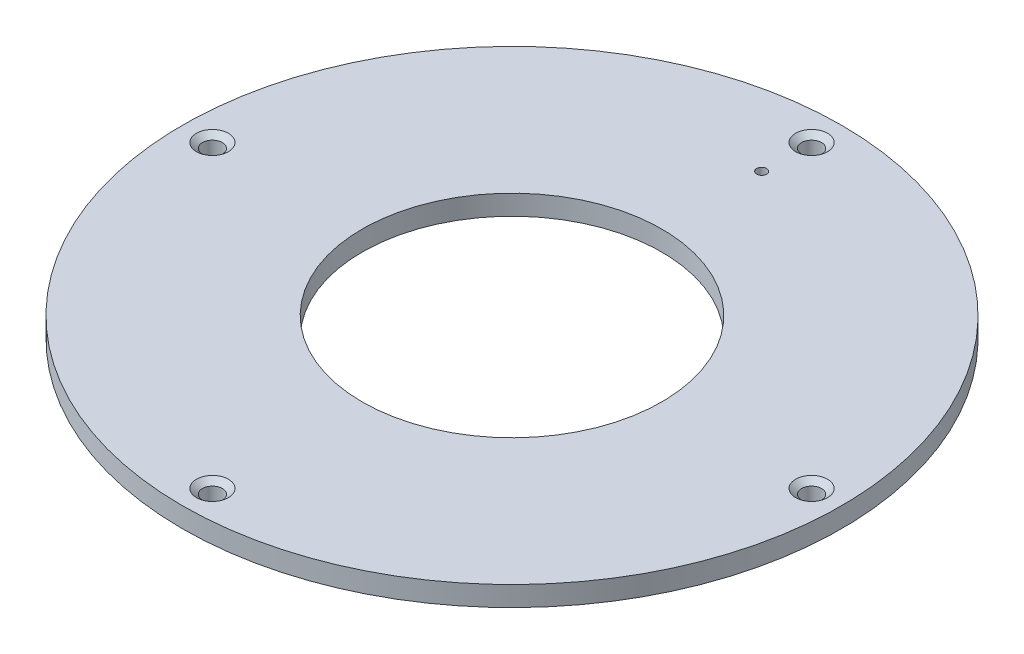
SolidWorks part; units mm, degrees
material "1060 Alloy"
ref_plane "Front Plane" through (0, 0, 0) normal (0, 0, 1) x (1, 0, 0)
ref_plane "Top Plane" through (0, 0, 0) normal (0, 1, 0) x (1, 0, 0)
ref_plane "Right Plane" through (0, 0, 0) normal (1, 0, 0) x (0, 0, -1)
sketch "Sketch1" plane through (0, 0, 0) normal (0, 1, 0) x (1, 0, 0)
  circle A0 centre (0, 0) radius 16.5
  dimension "D1" = 33
extrude "Boss-Extrude1" add sketch "Sketch1" along normal blind 1
sketch "Sketch2" plane through (0, 1, 0) normal (0, 1, 0) x (1, 0, 0)
  circle A0 centre (0, 0) radius 7.5
  dimension "D1" = 15
extrude "Cut-Extrude1" cut sketch "Sketch2" against normal through all both and the other way through all
ref_plane "Plane2" through (0, 0.5, 0) normal (0, 1, 0) x (1, 0, 0)
sketch "Sketch4" plane through (0, 1, 0) normal (0, 1, 0) x (1, 0, 0)
  circle A0 centre (0, 12.5) radius 0.25
  dimension "D1" = 0.5
  dimension "D2" = 12.5
extrude "Cut-Extrude2" cut sketch "Sketch4" against normal through all both and the other way through all
hole_wizard "CSK for M2 Flat Head Machine Screw1" positions "Sketch5" profile "Sketch6" countersink size "M2" standard "ANSI Metric" end condition through all
sketch "Sketch5" plane through (0, 1, 0) normal (0, 1, 0) x (1, 0, 0)
  point P0 (0, 15)
  point P2 (15, 0)
  point P4 (0, -15)
  point P6 (-15, 0)
  dimension "D1" = 15
  dimension "D2" = 15
  dimension "D3" = 15
  dimension "D4" = 15
sketch "Sketch6" plane through (0, 1, -15) normal (1, 0, 0) x (0, 0, 1)
  line L0 (0, 0) -> (0, 1)
  line L1 (0, 1) -> (0.5, 1)
  line L2 (0.5, 1) -> (0.5, 0.2517)
  line L3 (0.5, 0.2517) -> (0.8, 0)
  line L5 (0.8, 0) -> (0, 0)
  line L6 (-0.5, 0.2517) -> (-0.8, 0) construction
  line L11 (0, -6.35) -> (0, 107.95) construction
  dimension "Thru Hole Dia." = 1
  dimension "Thru Hole Depth" = 1
  dimension "Near C'Sink Dia." = 1.6
  dimension "Near C'Sink Angle" = 100
